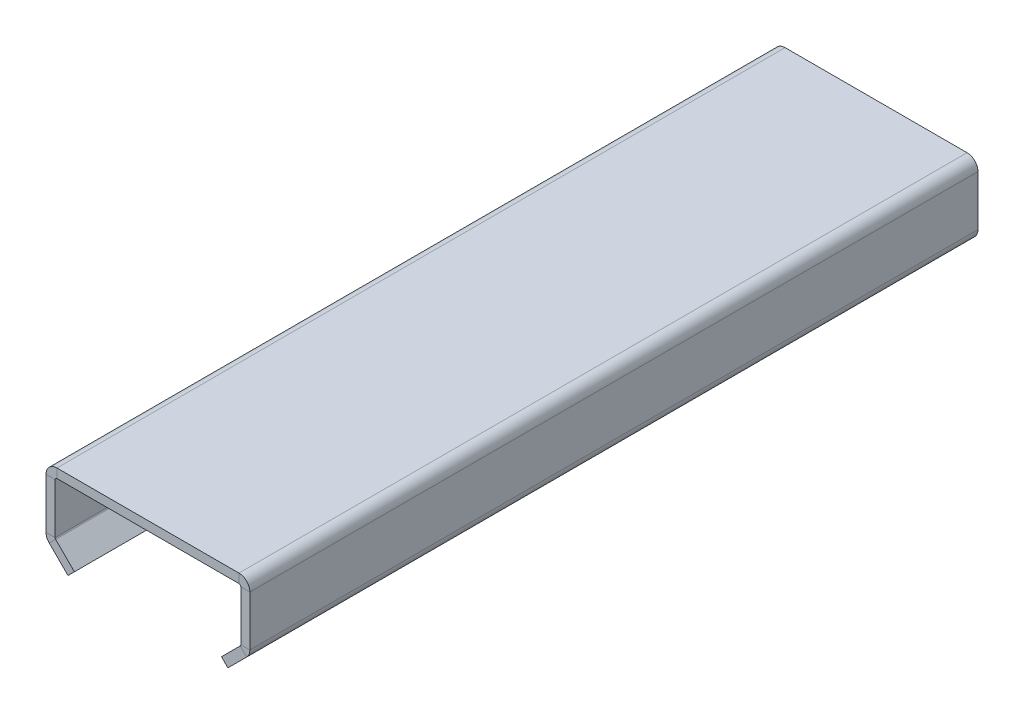
SolidWorks part; units mm, degrees
note: The reader was unsure of these and kept them because the rebuilt part matched: bend radius of "BaseBend1", "BaseBend2", "BaseBend3", "BaseBend4".
material "AISI 304"
ref_plane "Front Plane" through (0, 0, 0) normal (0, 0, 1) x (1, 0, 0)
ref_plane "Top Plane" through (0, 0, 0) normal (0, 1, 0) x (1, 0, 0)
ref_plane "Right Plane" through (0, 0, 0) normal (1, 0, 0) x (0, 0, -1)
sketch "Sketch1" plane through (0, 0, 0) normal (0, 0, 1) x (1, 0, 0)
  line L0 (0, 0) -> (-10.6066, 10.6066)
  line L1 (-10.6066, 10.6066) -> (-10.6066, 39.6066)
  line L2 (-10.6066, 39.6066) -> (91.3934, 39.6066)
  line L3 (0, 0) -> (0, 24.7429) construction
  line L4 (40.3934, 39.6066) -> (40.3934, 18.142) construction
  line L5 (80.7868, 0) -> (91.3934, 10.6066)
  line L6 (91.3934, 10.6066) -> (91.3934, 39.6066)
  dimension "D1" = 15
  dimension "D2" = 45
  dimension "D3" = 102
  dimension "D4" = 29
base flange "Base-Flange1" sketch "Sketch1" end condition mid plane depth 400 reverse direction no thickness 5 reverse thickness direction no bend radius 1
bend "BaseBend1" bend radius 1 bend angle 45 parameters "D5"=1
bend "BaseBend2" bend radius 1 bend angle 90 parameters "D5"=2
bend "BaseBend3" bend radius 1 bend angle 90 parameters "D5"=3
bend "BaseBend4" bend radius 1 bend angle 45 parameters "D5"=4
sketch "Bend-Lines1" [suppressed] plane through (0, 0, 0) normal (0, 1, 0) x (1, 0, 0)
sketch "Bounding-Box1" [suppressed] plane through (0, 0, 0) normal (0, 1, 0) x (1, 0, 0)
sheet metal parameters "Sheet-Metal1" thickness 5 parameters "D1"=1
flat pattern "Flat-Pattern1" [suppressed]
sketch "Bend-Lines2" plane through (0, 39.6066, 0) normal (0, -1, 0) x (-1, 0, 0)
  line L0 (44.0646, 200) -> (44.0646, -200) construction
  line L1 (12.3555, 200) -> (12.3555, -200) construction
  line L2 (-93.1423, -200) -> (-93.1423, 200) construction
  line L3 (-124.8514, -200) -> (-124.8514, 200) construction
  line L4 (44.0646, 200) -> (44.0646, -200) construction
  line L5 (12.3555, 200) -> (12.3555, -200) construction
  line L6 (-93.1423, -200) -> (-93.1423, 200) construction
  line L7 (-124.8514, -200) -> (-124.8514, 200) construction
sketch3d "Bounding-Box2" [suppressed]
  line L0 (49.4183, 0, 0) -> (49.4183, 400, 0) construction
  line L1 (-151.4183, 0, 0) -> (-151.4183, 400, 0) construction
  line L2 (49.4183, 0, 0) -> (-151.4183, 0, 0) construction
  line L3 (49.4183, 400, 0) -> (-151.4183, 400, 0) construction
bend of the flat pattern "Flatten-<BaseBend1>1"
bend of the flat pattern "Flatten-<BaseBend2>1"
bend of the flat pattern "Flatten-<BaseBend3>1"
bend of the flat pattern "Flatten-<BaseBend4>1"
